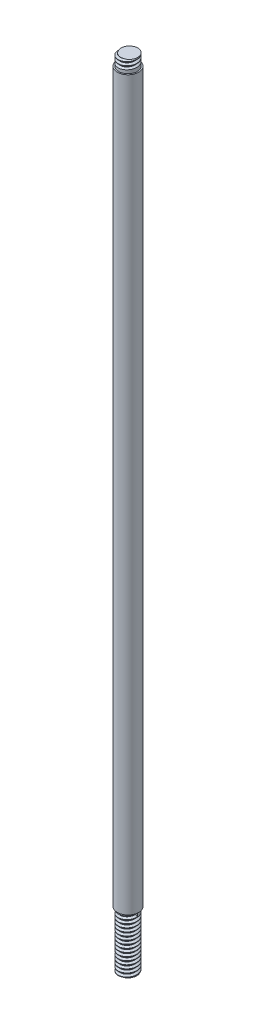
SolidWorks part; units mm, degrees
material "AISI 304"
ref_plane "Front Plane" through (0, 0, 0) normal (0, 0, 1) x (1, 0, 0)
ref_plane "Top Plane" through (0, 0, 0) normal (0, 1, 0) x (1, 0, 0)
ref_plane "Right Plane" through (0, 0, 0) normal (1, 0, 0) x (0, 0, -1)
sketch "Sketch1" plane through (0, 0, 0) normal (0, 1, 0) x (1, 0, 0)
  circle A0 centre (0, 0) radius 2.3813
  dimension "D1" = 4.7625
extrude "Boss-Extrude1" add sketch "Sketch1" along normal blind 177.8
sketch "Sketch2" plane through (0, 0, 0) normal (0, -1, 0) x (1, 0, 0)
  circle A0 centre (0, 0) radius 2.0828
  circle A1 centre (0, 0) radius 2.3813 construction
  circle A2 centre (0, 0) radius 2.3813
  dimension "D1" = 4.1656
extrude "Cut-Extrude1" cut sketch "Sketch2" against normal blind 12.7
thread "Thread1" pitch 0.7937 method cut profile "Thread Profile1" start angle 0, offset 1, length 12.7, pitch 0.7937, diameter 4.1656
ref_plane "Plane1" through (2.0828, -1, 0) normal (0, 0, 1) x (1, 0, 0)
sketch "Thread Profile1" plane through (2.0828, -1, 0) normal (0, 0, 1) x (1, 0, 0)
  line L0 (0, 0) -> (0, 0.7937) construction
  line L11 (0, 0) -> (0, 0.6945)
  line L12 (0, 0.6945) -> (-0.4296, 0.4465)
  line L13 (-0.4296, 0.4465) -> (-0.4296, 0.248)
  line L15 (-0.4296, 0.248) -> (0, 0)
  line L17 (-0.4296, 0.3473) -> (0, 0.3473) construction
  point P2 (0, 0)
  dimension "Pitch" = 0.7937
  dimension "Profile_Angle" = 60
  dimension "Profile_Land" = 0.1984
  dimension "Profile_Height" = 0.4296
sketch "Sketch3" plane through (0, 177.8, 0) normal (0, 1, 0) x (1, 0, 0)
  circle A0 centre (0, 0) radius 2.0856
  circle A1 centre (0, 0) radius 2.3813 construction
  circle A2 centre (0, 0) radius 2.3813
extrude "Cut-Extrude2" cut sketch "Sketch3" against normal blind 2.54
thread "Thread2" pitch 0.7937 method cut profile "Thread Profile2" start angle 0, offset 1, length 2.54, pitch 0.7937, diameter 4.1712
ref_plane "Plane2" through (-2.0856, 178.8, 0) normal (0, 0, 1) x (-1, 0, 0)
sketch "Thread Profile2" plane through (-2.0856, 178.8, 0) normal (0, 0, 1) x (-1, 0, 0)
  line L0 (0, 0) -> (0, 0.7937) construction
  line L11 (0, 0) -> (0, 0.6945)
  line L12 (0, 0.6945) -> (-0.4296, 0.4465)
  line L13 (-0.4296, 0.4465) -> (-0.4296, 0.248)
  line L15 (-0.4296, 0.248) -> (0, 0)
  line L17 (-0.4296, 0.3473) -> (0, 0.3473) construction
  point P2 (0, 0)
  dimension "Pitch" = 0.7937
  dimension "Profile_Angle" = 60
  dimension "Profile_Land" = 0.1984
  dimension "Profile_Height" = 0.4296
